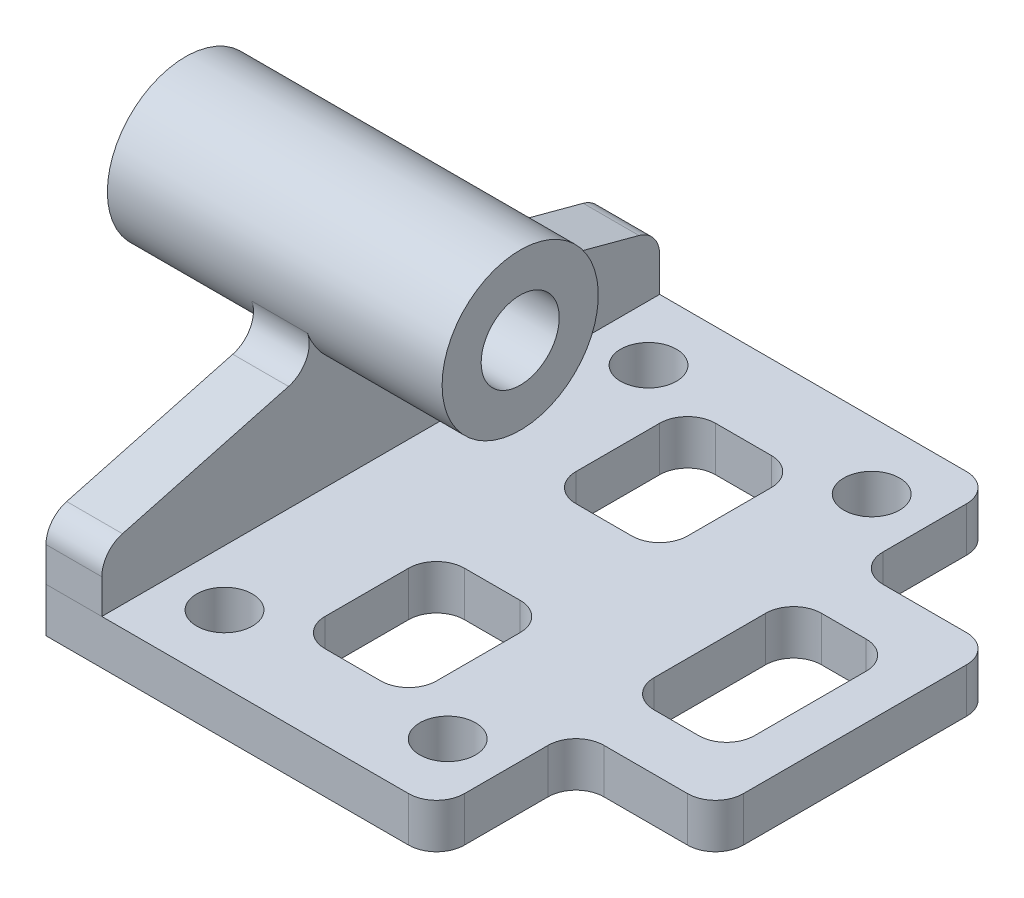
SolidWorks part; units mm, degrees
note: The reader was unsure of these and kept them because the rebuilt part matched: shared geometry of "Sketch3<3>".
material "1060 Alloy"
ref_plane "Front Plane" through (0, 0, 0) normal (0, 0, 1) x (1, 0, 0)
ref_plane "Top Plane" through (0, 0, 0) normal (0, 1, 0) x (1, 0, 0)
ref_plane "Right Plane" through (0, 0, 0) normal (1, 0, 0) x (0, 0, -1)
sketch "Sketch1" plane through (0, 0, 0) normal (0, 1, 0) x (1, 0, 0)
  line L0 (40, 100) -> (40, 0) construction
  line L1 (0, 100) -> (70, 100)
  line L2 (0, 100) -> (0, 0)
  line L3 (0, 0) -> (70, 0)
  line L4 (95, 75) -> (95, 25)
  line L6 (70, 100) -> (70, 75)
  line L7 (70, 75) -> (95, 75)
  line L9 (70, 25) -> (95, 25)
  line L10 (70, 25) -> (70, 0)
  line L13 (0, 50) -> (95, 50) construction
  line L14 (70, 12) -> (0, 12) construction
  line L15 (60, 0) -> (60, 100) construction
  line L16 (30, 85) -> (50, 85)
  line L17 (30, 40) -> (50, 40)
  line L18 (30, 40) -> (30, 15)
  line L19 (30, 15) -> (50, 15)
  line L20 (50, 40) -> (50, 15)
  line L21 (50, 60) -> (50, 85)
  line L22 (30, 60) -> (50, 60)
  line L23 (30, 60) -> (30, 85)
  line L25 (69, 65) -> (87, 65)
  line L26 (69, 65) -> (69, 35)
  line L27 (69, 35) -> (87, 35)
  line L28 (87, 65) -> (87, 35)
  circle A0 centre (60, 12) radius 5
  circle A1 centre (20, 12) radius 5
  circle A2 centre (20, 88) radius 5
  circle A3 centre (60, 88) radius 5
  point P19 (40, 40)
  point P38 (82.5, 25)
  dimension "D5" = 10
  dimension "D7" = 15
  dimension "D1" = 20
  dimension "D2" = 100
  dimension "D3" = 70
  dimension "D4" = 10
  dimension "D6" = 40
  dimension "D8" = 20
  dimension "D9" = 25
  dimension "D10" = 12
  dimension "D11" = 50
  dimension "D12" = 18
  dimension "D13" = 30
  dimension "D14" = 10
  dimension "D15" = 8
extrude "Boss-Extrude1" add sketch "Sketch1" along normal blind 8
fillet "Fillet1" radius 5 18 edges at (70, 4, -25) (70, 4, 0) (95, 4, -25) (95, 4, -75) (70, 4, -100) (70, 4, -75) (87, 4, -65) (69, 4, -65) (87, 4, -35) (69, 4, -35) (50, 4, -15) (50, 4, -40) (30, 4, -40) (30, 4, -15) (30, 4, -60) (50, 4, -85) (50, 4, -60) (30, 4, -85)
sketch "Sketch3" plane through (0, 0, 0) normal (-1, 0, 0) x (0, 0, 1)
  line L0 (-100, 8) -> (-100, 18)
  line L1 (-100, 18) -> (-50, 31.3975)
  line L2 (-50, 31.3975) -> (0, 18)
  line L3 (0, 18) -> (0, 8)
  line L4 (-100, 0) -> (0, 0)
  line L5 (0, 0) -> (0, 8)
  line L6 (0, 8) -> (-100, 8)
  line L7 (-100, 8) -> (-100, 0)
  line L8 (-100, 0) -> (0, 0)
  line L9 (0, 0) -> (0, 8)
  line L11 (-100, 8) -> (-100, 0)
  line L14 (-100, 8) -> (0, 8) construction
  circle A1 centre (-50, 38.3975) radius 7
  circle A2 centre (-50, 38.3975) radius 14
  point P2 (-50, 0)
  dimension "D4" = 14
  dimension "D5" = 28
  dimension "D2" = 18
  dimension "D3" = 15
  dimension "D1" = 0
extrude "Boss-Extrude2" add sketch "Sketch3" against normal blind 10 separate body
extrude "Boss-Extrude3" add sketch "Sketch3<3>" along normal blind 25 and the other way blind 35
sketch "Sketch3<3>" plane through (0, 0, 0) normal (-1, 0, 0) x (0, 0, 1) same geometry as "Sketch3"
fillet "Fillet2" radius 5 4 edges at (5, 18, -100) (5, 18, 0) (5, 28.6935, -60.0913) (5, 28.6935, -39.9087)
